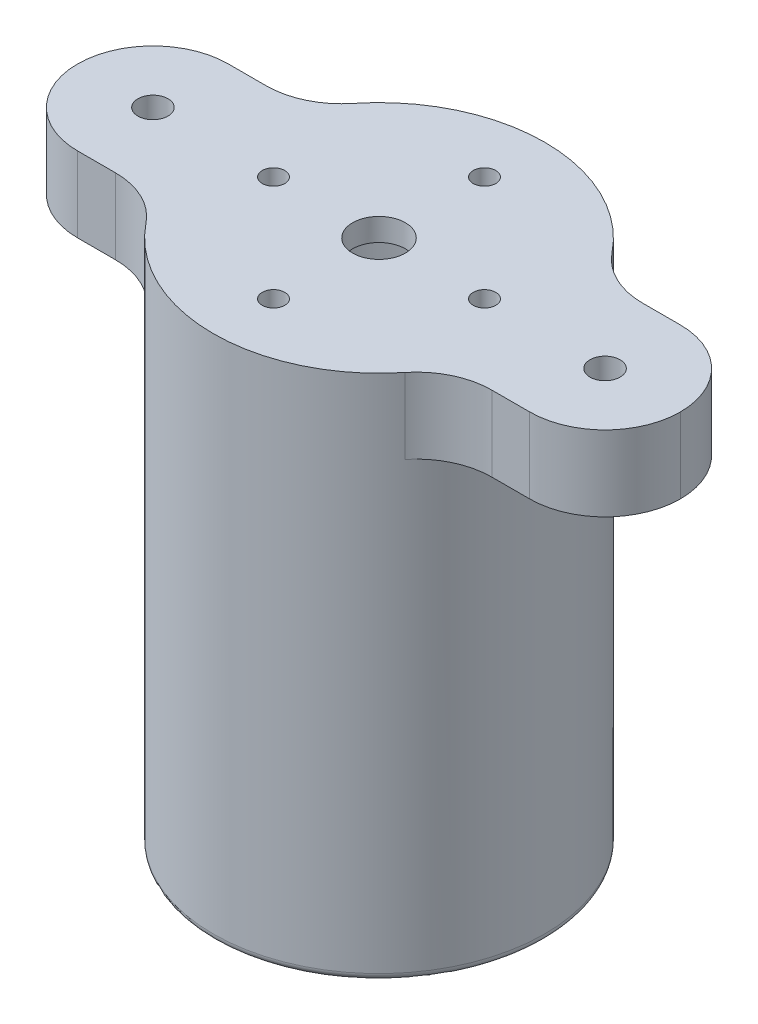
SolidWorks part; units mm, degrees
material "ABS"
ref_plane "Front Plane" through (0, 0, 0) normal (0, 0, 1) x (1, 0, 0)
ref_plane "Top Plane" through (0, 0, 0) normal (0, 1, 0) x (1, 0, 0)
ref_plane "Right Plane" through (0, 0, 0) normal (1, 0, 0) x (0, 0, -1)
sketch "Sketch3" plane through (0, 0, 0) normal (0, 1, 0) x (1, 0, 0)
  circle A0 centre (0, 0) radius 22
extrude "Boss-Extrude1" add sketch "Sketch3" along normal blind 70
sketch "Sketch14" plane through (0, 70, 0) normal (0, 1, 0) x (1, 0, 0)
  line L1 (-40, 10) -> (40, 10)
  line L2 (-40, 10) -> (-40, -10)
  line L3 (-40, -10) -> (40, -10)
  line L4 (40, 10) -> (40, -10)
  line L5 (-40, 10) -> (40, -10) construction
  line L6 (-40, -10) -> (40, 10) construction
  point P0 (0, 0)
extrude "Boss-Extrude3" add sketch "Sketch14" against normal blind 10
sketch "Sketch4" plane through (0, 0, 0) normal (0, -1, 0) x (-1, 0, 0)
  circle A0 centre (0, 0) radius 19
extrude "Cut-Extrude1" cut sketch "Sketch4" against normal blind 65
sketch "Sketch5" plane through (0, 70, 0) normal (0, 1, 0) x (1, 0, 0)
  circle A0 centre (0, 0) radius 3.5
extrude "Cut-Extrude2" cut sketch "Sketch5" against normal blind 5
sketch "Sketch7" plane through (0, 70, 0) normal (0, 1, 0) x (1, 0, 0)
  circle A0 centre (0, -14) radius 1.5
  circle A1 centre (0, 14) radius 1.5
  circle A2 centre (14, 0) radius 1.5
  circle A3 centre (-14, 0) radius 1.5
extrude "Cut-Extrude3" cut sketch "Sketch7" against normal blind 5
sketch "Sketch15" plane through (0, 70, 0) normal (0, 1, 0) x (1, 0, 0)
  circle A0 centre (30, 0) radius 2
  circle A1 centre (-30, 0) radius 2
extrude "Cut-Extrude6" cut sketch "Sketch15" against normal blind 10
fillet "Fillet1" radius 10 2 edges at (40, 65, -10) (40, 65, 10)
fillet "Fillet2" radius 10 2 edges at (-40, 65, -10) (-40, 65, 10)
fillet "Fillet3" radius 10 4 edges at (-19.5959, 65, 10) (-19.5959, 65, -10) (19.5959, 65, -10) (19.5959, 65, 10)
fillet "Fillet4" radius 1 2 edges at (0, 0, -19) (0, 0, 22)
sketch "Sketch16" plane through (0, 65, 0) normal (0, -1, 0) x (1, 0, 0)
  circle A0 centre (0, 0) radius 11
extrude "Cut-Extrude7" cut sketch "Sketch16" against normal blind 2
